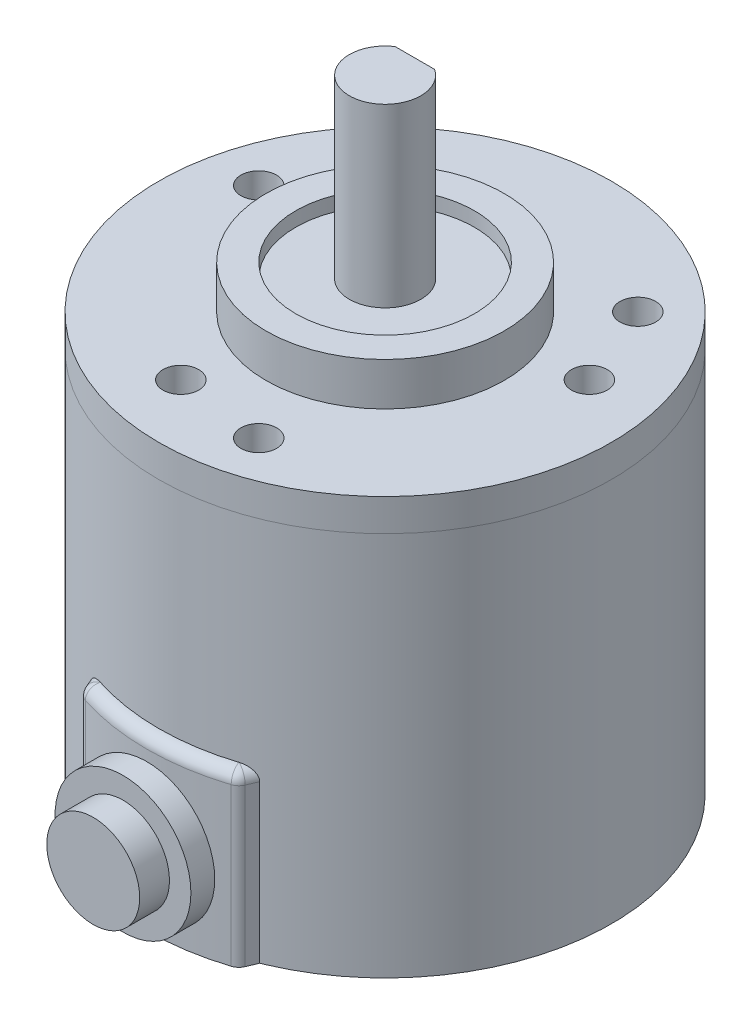
SolidWorks part; units mm, degrees
ref_plane "Front Plane" through (0, 0, 0) normal (0, 0, 1) x (1, 0, 0)
ref_plane "Top Plane" through (0, 0, 0) normal (0, 1, 0) x (1, 0, 0)
ref_plane "Right Plane" through (0, 0, 0) normal (1, 0, 0) x (0, 0, -1)
sketch "Sketch2" plane through (0, 0, 0) normal (0, 1, 0) x (1, 0, 0)
  circle A0 centre (0, 0) radius 19
  dimension "D1" = 38
extrude "Boss-Extrude1" add sketch "Sketch2" along normal blind 32.3
sketch "Sketch3" plane through (0, 32.3, 0) normal (0, 1, 0) x (1, 0, 0)
  circle A1 centre (0, 0) radius 19
  circle A2 centre (0, 0) radius 19
  dimension "D1" = 0
extrude "Boss-Extrude2" add sketch "Sketch3" along normal blind 2.7 separate body
sketch "Sketch4" plane through (0, 35, 0) normal (0, 1, 0) x (1, 0, 0)
  line L0 (0, 0) -> (3.8823, -14.4889) construction
  line L1 (0, 0) -> (-3.6235, -13.523) construction
  line L2 (0, 0) -> (0, -27.9142) construction
  circle A0 centre (0, 0) radius 10
  circle A1 centre (0, 0) radius 14 construction
  circle A2 centre (0, 0) radius 15 construction
  circle A3 centre (-3.6235, -13.523) radius 1.5
  circle A4 centre (-9.8995, 9.8995) radius 1.5
  circle A5 centre (13.523, 3.6235) radius 1.5
  circle A6 centre (3.8823, -14.4889) radius 1.5
  circle A7 centre (-14.4889, 3.8823) radius 1.5
  circle A8 centre (10.6066, 10.6066) radius 1.5
  point P13 (0, 0)
  point P20 (0, 0)
  dimension "D1" = 20
  dimension "D2" = 28
  dimension "D3" = 30
  dimension "D4" = 3
  dimension "D6" = 3
  dimension "D8" = 30
  dimension "D9" = 15
  dimension "D5" = 3
  dimension "D7" = 3
extrude "Cut-Extrude1" cut sketch "Sketch4" against normal blind 6 contours A4 | A7 | A3 | A6 | A5 | A8 region at (-3.6235, 35, 13.523) region at (-9.8995, 35, -9.8995) region at (13.523, 35, -3.6235) region at (3.8823, 35, 14.4889) region at (-14.4889, 35, -3.8823) region at (10.6066, 35, -10.6066)
extrude "Boss-Extrude3" add sketch "Sketch4<3>" along normal blind 3.6 contours A0 region at (0, 35, 0)
sketch "Sketch4<3>" plane through (0, 35, 0) normal (0, 1, 0) x (1, 0, 0) same geometry as "Sketch4"
sketch "Sketch5" plane through (0, 38.6, 0) normal (0, 1, 0) x (1, 0, 0)
  circle A0 centre (0, 0) radius 7.5
  dimension "D1" = 15
extrude "Cut-Extrude2" cut sketch "Sketch5" against normal blind 1.2
sketch "Sketch6" plane through (0, 37.4, 0) normal (0, 1, 0) x (1, 0, 0)
  circle A0 centre (0, 0) radius 3
  dimension "D1" = 6
extrude "Boss-Extrude4" add sketch "Sketch6" along normal blind 14.8
sketch "Sketch7" plane through (0, 52.2, 0) normal (0, 1, 0) x (1, 0, 0)
  line L0 (-1.6583, 2.5) -> (1.6583, 2.5)
  circle A0 centre (0, 0) radius 3 construction
  circle M2 centre (0, 0) radius 3
  dimension "D1" = 2.5
extrude "Cut-Extrude3" cut sketch "Sketch7" against normal blind 10 and the other way through all contours L0 M2 region at (0, 52.2, -2.7015)
sketch "Sketch8" plane through (0, 0, 0) normal (0, -1, 0) x (1, 0, 0)
  line L0 (0, 0) -> (0, 20)
  line L1 (0, 0) -> (-7.1, 17.6236)
  line L2 (-7.1, 17.6236) -> (-6.5593, 18.8938)
  line L3 (-7.1, 17.6236) -> (-1.3074, 19.9572) construction
  line L4 (0, 0) -> (7.1, 17.6236)
  line L5 (7.1, 17.6236) -> (6.5593, 18.8938)
  circle A0 centre (0, 0) radius 20
  circle A1 centre (0, 0) radius 19 construction
  point P5 (-1.233, 19.962)
  circle M6 centre (0, 0) radius 19
  dimension "D1" = 40
  dimension "D2" = 7.1
  dimension "D3" = 45
extrude "Boss-Extrude5" add sketch "Sketch8" against normal blind 14.2 separate body contours L3 L0 A0 M6 | L2 L3 A0 | L5 A0 L0 M6 region at (-1.9298, 0, 19.2316) region at (3.4528, 0, 19.0784) region at (-4.8072, 0, 18.942)
fillet "Fillet1" radius 1 5 edges at (6.8297, 14.2, 18.2587) (-6.8297, 14.2, 18.2587) (6.5593, 7.1, 18.8938) (-6.5593, 7.1, 18.8938) (0, 14.2, 20)
ref_plane "Plane1" through (0, 0, 20) normal (0, 0, 1) x (1, 0, 0)
sketch "Sketch9" plane through (0, 0, 20) normal (0, 0, 1) x (1, 0, 0)
  line L0 (6.1215, 0) -> (6.1215, 13.2) construction
  circle A0 centre (0, 6.6) radius 5.7
  point P2 (0, 0)
  point P4 (0, 0)
  point P7 (6.1215, 6.6)
  dimension "D1" = 11.4
extrude "Boss-Extrude6" add sketch "Sketch9" along normal blind 2 separate body
sketch "Sketch10" plane through (0, 0, 22) normal (0, 0, 1) x (1, 0, 0)
  circle A0 centre (0, 6.6) radius 3.9
  circle A1 centre (0, 6.6) radius 5.7 construction
  dimension "D1" = 7.8
extrude "Boss-Extrude7" add sketch "Sketch10" along normal blind 2.5
equation "\"base_d\"= 38"
equation "\"base_ht\"= 35"
equation "\"base_silver_ht\"= 2.7"
equation "\"base_black_ht\"= \"base_ht\" - \"base_silver_ht\""
equation "\"base_outer_c\"= 40"
equation "\"base_outer_sq\"= 14.2"
equation "\"base_outer_sq_oc_d\"= 11.4"
equation "\"base_outer_oc_ht\"= 2"
equation "\"base_outer_ic_d\"= 7.8"
equation "\"base_outer_ic_ht\"= 2.5"
equation "\"screw_d\"= 3"
equation "\"screw_outer guide\"= 30"
equation "\"screw_inner_guide\"= 28"
equation "\"screw_angle\"= 30"
equation "\"screw_align_angle\"= 15"
equation "\"middle_od\"= 20"
equation "\"middle_id\"= 15"
equation "\"middle_ht\"= 3.6"
equation "\"middle_dep\"= 1.2"
equation "\"shaft_ht\"= 14.8"
equation "\"shaft_dep\"= 10"
equation "\"shaft_d\"= 6"
equation "\"shaft_id\"= 2.5"
equation "\"screw_len\"= 6"
